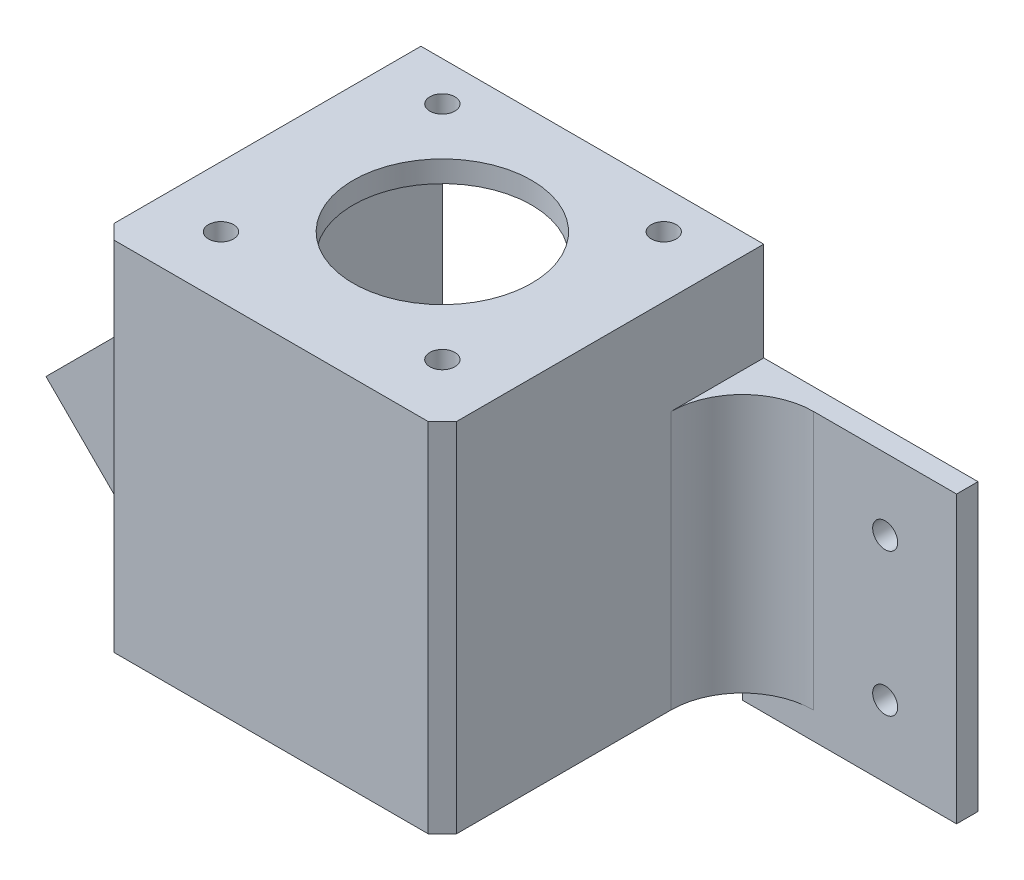
SolidWorks part; units mm, degrees
ref_plane "Front Plane" through (0, 0, 0) normal (0, 0, 1) x (1, 0, 0)
ref_plane "Top Plane" through (0, 0, 0) normal (0, 1, 0) x (1, 0, 0)
ref_plane "Right Plane" through (0, 0, 0) normal (1, 0, 0) x (0, 0, -1)
sketch "Sketch1" plane through (0, 0, 0) normal (0, 1, 0) x (1, 0, 0)
  line L0 (-24, 21) -> (-24, -24)
  line L1 (-21, 21) -> (21, 21) construction
  line L2 (-21, 21) -> (-21, -21) construction
  line L3 (-21, -21) -> (21, -21) construction
  line L4 (21, 21) -> (21, -21) construction
  line L5 (-21, 21) -> (21, -21) construction
  line L6 (-21, -21) -> (21, 21) construction
  line L7 (-24, -24) -> (24, -24)
  line L8 (24, 21) -> (24, -24)
  line L9 (-24, 21) -> (24, 21)
  point P0 (0, 0)
  dimension "D1" = 42
  dimension "D2" = 3
extrude "Boss-Extrude1" add sketch "Sketch1" along normal blind 3
sketch "Sketch2" plane through (0, 0, 0) normal (0, -1, 0) x (1, 0, 0)
  line L1 (-21, 21) -> (21, 21)
  line L2 (-21, 21) -> (-21, -21)
  line L4 (21, 21) -> (21, -21)
  line L5 (-21, 21) -> (21, -21) construction
  line L6 (-21, -21) -> (21, 21) construction
  line L7 (24, -21) -> (-24, -21) construction
  line L8 (21, -21) -> (24, -21)
  line L9 (-24, 24) -> (24, 24)
  line L10 (-24, 24) -> (-24, -21)
  line L11 (-24, -21) -> (-21, -21)
  line L12 (24, 24) -> (24, -21)
  point P0 (0, 0)
  dimension "D1" = 42
extrude "Boss-Extrude2" add sketch "Sketch2" along normal blind 47
sketch "Sketch3" plane through (24, 0, 0) normal (1, 0, 0) x (0, 0, -1)
  line L1 (21, -10.8) -> (18, -10.8)
  line L2 (21, -10.8) -> (21, -50.8)
  line L3 (21, -50.8) -> (18, -50.8)
  line L4 (18, -10.8) -> (18, -50.8)
  line L5 (21, 3) -> (21, -47) construction
  line L6 (-24, 3) -> (21, 3) construction
  point P10 (0, 0)
  point P11 (0, 0)
  dimension "D1" = 3
  dimension "D2" = 40
  dimension "D3" = 13.8
extrude "Boss-Extrude3" add sketch "Sketch3" along normal blind 30
sketch "Sketch4" plane through (0, 0, -21) normal (0, 0, -1) x (-1, 0, 0)
  line L0 (24, -10.8) -> (73.4975, -60.2975)
  line L1 (73.4975, -60.2975) -> (45.2132, -88.5817)
  line L2 (45.2132, -88.5817) -> (24, -67.3685)
  line L3 (24, 3) -> (24, -47) construction
  line L4 (24, -10.8) -> (24, -67.3685)
  point P2 (24, -58.0814)
  point P5 (0, 0)
  point P7 (0, 0)
  point P9 (0, 0)
  point P10 (24, -10.838)
  point P11 (0, 0)
  point P12 (25.9114, -50.8829)
  dimension "D1" = 45
  dimension "D2" = 30
  dimension "D3" = 40
extrude "Boss-Extrude4" add sketch "Sketch4" against normal blind 3
fillet "Fillet1" radius 10 2 edges at (-24, -28.9, -18) (24, -28.9, -18)
chamfer "Chamfer1" distance 2 angle 45 2 edges at (-24, -22, 24) (24, -22, 24)
sketch "Sketch5" plane through (0, 0, 0) normal (0, -1, 0) x (1, 0, 0)
  line L7 (-15.5, 15.5) -> (15.5, 15.5) construction
  line L8 (-15.5, 15.5) -> (-15.5, -15.5) construction
  line L9 (-15.5, -15.5) -> (15.5, -15.5) construction
  line L10 (15.5, 15.5) -> (15.5, -15.5) construction
  line L11 (-15.5, 15.5) -> (15.5, -15.5) construction
  line L12 (-15.5, -15.5) -> (15.5, 15.5) construction
  circle A0 centre (-15.5, 15.5) radius 1.75
  circle A1 centre (15.5, 15.5) radius 1.75
  circle A2 centre (15.5, -15.5) radius 1.75
  circle A3 centre (-15.5, -15.5) radius 1.75
  circle A4 centre (0, 0) radius 12.5
  point P0 (0, 0)
  dimension "D2" = 4
  dimension "D3" = 3.5
  dimension "D4" = 25
  dimension "D1" = 31
extrude "Cut-Extrude1" cut sketch "Sketch5" against normal through all
ref_plane "Plane1" through (0, -37, 0) normal (0, -1, 0) x (-1, 0, 0)
sketch "Sketch6" plane through (0, -37, 0) normal (0, -1, 0) x (-1, 0, 0)
  line L0 (24, 3.8579) -> (38.1421, 18)
  line L2 (73.4975, 18) -> (34, 18) construction
  line L3 (24, -22) -> (24, 8) construction
  line L4 (24, 18) -> (45.2132, 18) construction
  point P2 (22.991, 32.1421)
  point P3 (26.0764, 3.742)
  point P6 (24, 32.1421)
  point P7 (24, 0.9155)
  point P10 (39.66, 18)
  dimension "D1" = 45
  dimension "D2" = 20
sketch "Sketch7" plane through (0, 0, -18) normal (0, 0, 1) x (1, 0, 0)
  line L0 (44, -10.8) -> (44, -50.8) construction
  line L1 (54, -10.8) -> (34, -10.8) construction
  line L2 (54, -50.8) -> (24, -50.8) construction
  line L3 (-53.7487, -40.5487) -> (-25.4645, -68.833) construction
  line L4 (-73.4975, -60.2975) -> (-34, -20.8) construction
  line L5 (54, -50.8) -> (24, -50.8) construction
  line L6 (-45.2132, -88.5817) -> (-73.4975, -60.2975) construction
  line L7 (-53.7487, -40.5487) -> (-73.4975, -60.2975) construction
  line L8 (-63.6231, -50.4231) -> (-35.3388, -78.7074) construction
  line L9 (-24, -67.3685) -> (-45.2132, -88.5817) construction
  line L10 (-24, -67.3685) -> (-45.2132, -88.5817) construction
  circle A0 centre (44, -20.8) radius 1.75
  circle A1 centre (44, -40.8) radius 1.75
  circle A2 centre (-56.552, -57.4942) radius 1.75
  circle A3 centre (-42.4099, -71.6363) radius 1.75
  dimension "D1" = 10
  dimension "D3" = 3.5
  dimension "D4" = 3.5
  dimension "D5" = 3.5
  dimension "D7" = 3.5
  dimension "D2" = 10
  dimension "D6" = 10
  dimension "D8" = 10
extrude "Cut-Extrude2" cut sketch "Sketch7" against normal through all
